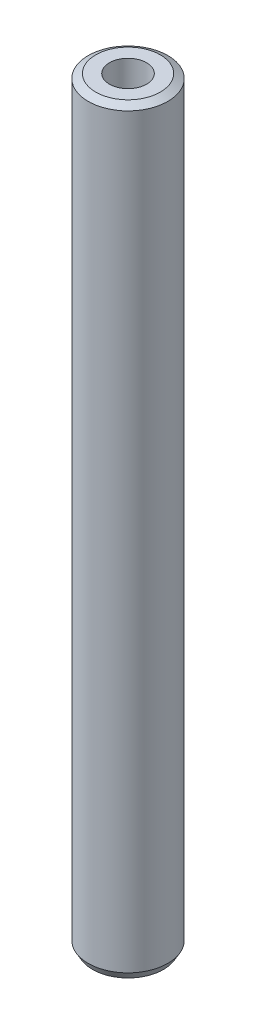
SolidWorks part; units mm, degrees
ref_plane "Front Plane" through (0, 0, 0) normal (0, 0, 1) x (1, 0, 0)
ref_plane "Top Plane" through (0, 0, 0) normal (0, 1, 0) x (1, 0, 0)
ref_plane "Right Plane" through (0, 0, 0) normal (1, 0, 0) x (0, 0, -1)
sketch "Sketch1" plane through (0, 0, 0) normal (0, 1, 0) x (1, 0, 0)
  circle A0 centre (0, 0) radius 22.5
  dimension "SHAFT_OD" = 45
extrude "Boss-Extrude1" add sketch "Sketch1" along normal blind 428.8114
sketch "Sketch2" plane through (0, 0, 0) normal (0, 1, 0) x (1, 0, 0)
  circle A0 centre (0, 0) radius 10.5265
  dimension "BORE_D" = 21.053
extrude "Cut-Extrude1" cut sketch "Sketch2" along normal through all
chamfer "Chamfer1" distance 2.4456 angle 60 2 edges at (0, 428.8114, 22.5) (0, 0, 22.5) first distance on face at (0, 428.8114, 22.5) first distance on face at (0, 0, 10.5265)
